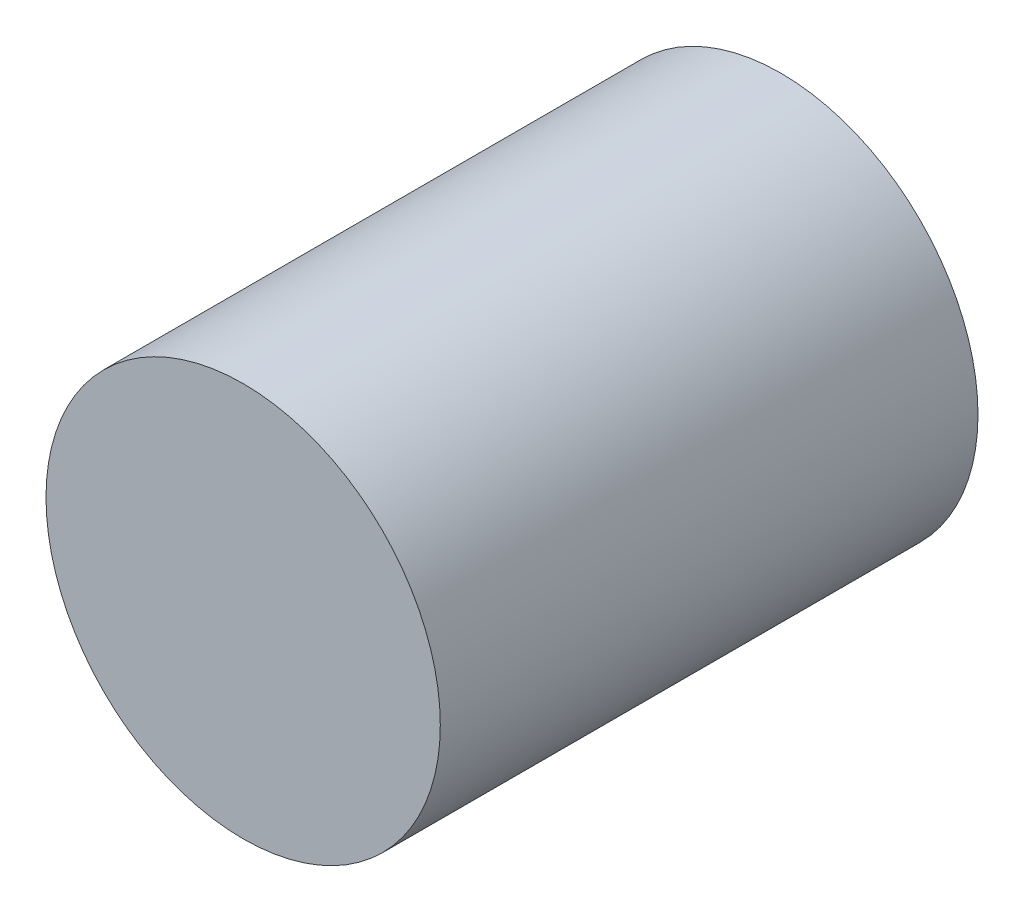
SolidWorks part; units mm, degrees
ref_plane "Front Plane" through (0, 0, 0) normal (0, 0, 1) x (1, 0, 0)
ref_plane "Top Plane" through (0, 0, 0) normal (0, 1, 0) x (1, 0, 0)
ref_plane "Right Plane" through (0, 0, 0) normal (1, 0, 0) x (0, 0, -1)
sketch "Sketch1" plane through (0, 0, 0) normal (0, 0, 1) x (1, 0, 0)
  circle A0 centre (0, 0) radius 22
  dimension "D1" = 44
extrude "Boss-Extrude1" add sketch "Sketch1" along normal mid plane 60
